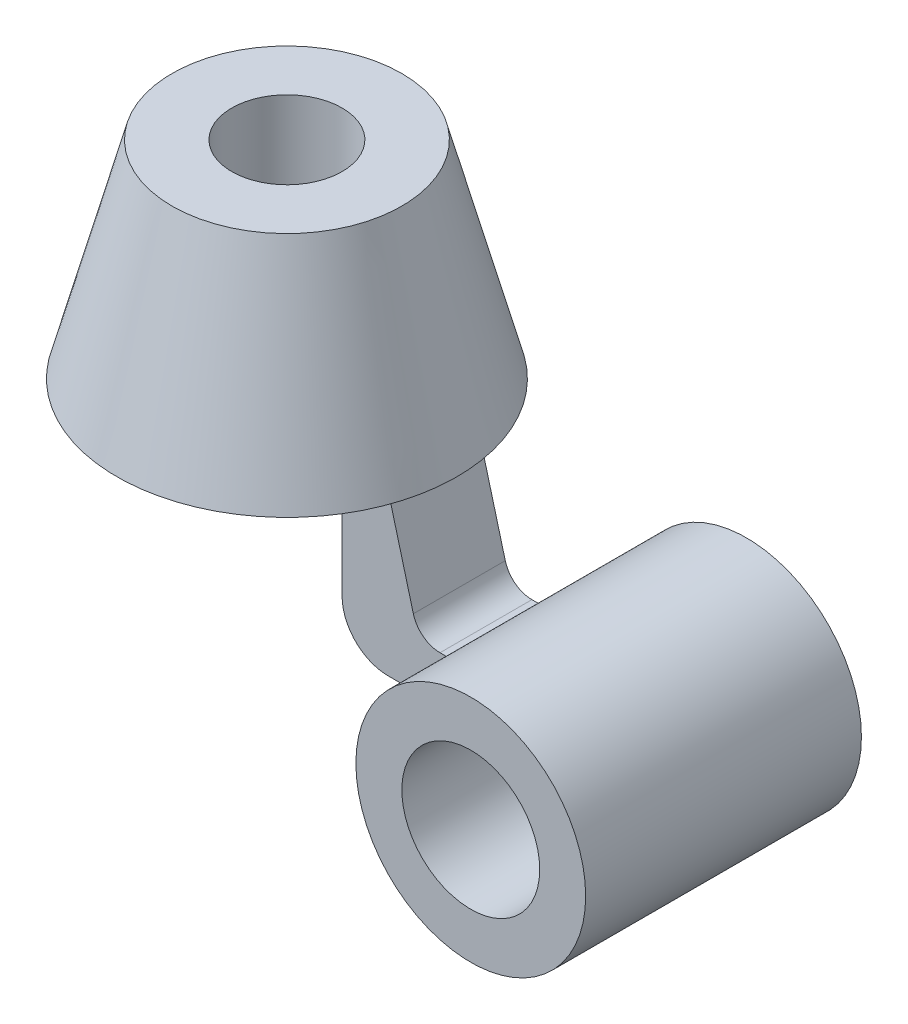
SolidWorks part; units mm, degrees
ref_plane "Front Plane" through (0, 0, 0) normal (0, 0, 1) x (1, 0, 0)
ref_plane "Top Plane" through (0, 0, 0) normal (0, 1, 0) x (1, 0, 0)
ref_plane "Right Plane" through (0, 0, 0) normal (1, 0, 0) x (0, 0, -1)
sketch "Sketch1" plane through (0, 0, 0) normal (0, 0, 1) x (1, 0, 0)
  line L0 (45, 0) -> (32, 0)
  line L1 (22, 10) -> (22, 35)
  line L2 (22, 35) -> (32, 35)
  line L3 (32, 35) -> (37.5071, 14.4471)
  line L4 (43.3027, 10) -> (47.0871, 10)
  circle A0 centre (70, 0) radius 25
  circle A1 centre (70, 0) radius 15
  arc A2 (37.5071, 14.4471) -> (43.3027, 10) centre (43.3027, 16) ccw
  arc A3 (32, 0) -> (22, 10) centre (32, 10) cw
  point P5 (0, 0)
  point P10 (76.3448, 0)
  dimension "D1" = 30
  dimension "D2" = 50
  dimension "D9" = 6
  dimension "D10" = 10
  dimension "D3" = 10
  dimension "D4" = 10
  dimension "D5" = 15
  dimension "D6" = 22
  dimension "D7" = 70
  dimension "D8" = 35
extrude "Boss-Extrude1" add sketch "Sketch1" along normal mid plane 60 contours A0 A1 region at (46.2195, 4.9633, 0)
extrude "Boss-Extrude2" add sketch "Sketch1<3>" along normal mid plane 20 contours A3 L0 A0 L4 A2 L3 L2 L1 region at (31.2262, 15.1094, 0)
sketch "Sketch1<3>" plane through (0, 0, 0) normal (0, 0, 1) x (1, 0, 0) same geometry as "Sketch1"
sketch "Sketch2" plane through (0, 0, 0) normal (0, 0, 1) x (1, 0, 0)
  line L0 (0, 35) -> (0, 80) construction
  line L1 (12, 80) -> (12, 35)
  line L2 (12, 35) -> (37, 35)
  line L3 (37, 35) -> (25, 80)
  line L4 (25, 80) -> (12, 80)
  point P5 (0, 0)
  point P8 (0, 0)
  point P10 (0, 0)
  dimension "D1" = 24
  dimension "D2" = 74
  dimension "D3" = 50
  dimension "D4" = 45
revolve "Revolve1" add sketch "Sketch2" angle 360 about L0
